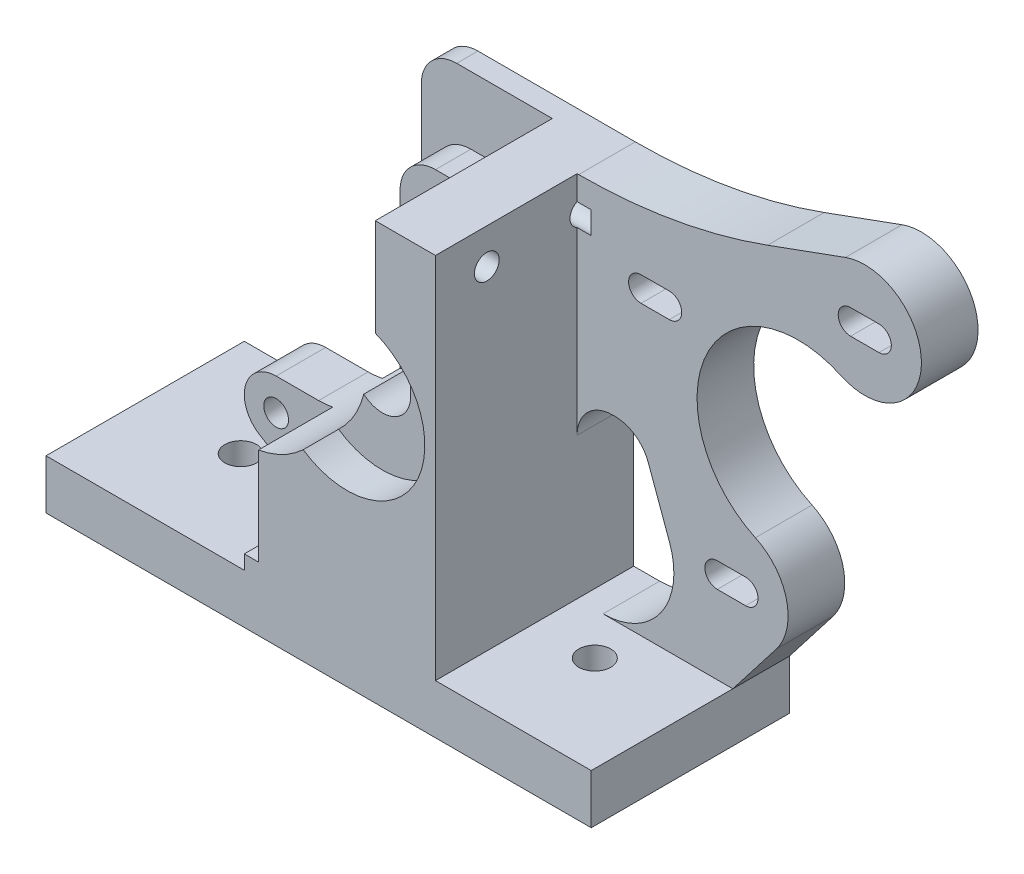
SolidWorks part; units mm, degrees
ref_plane "Front Plane" through (0, 0, 0) normal (0, 0, 1) x (1, 0, 0)
ref_plane "Top Plane" through (0, 0, 0) normal (0, 1, 0) x (1, 0, 0)
ref_plane "Right Plane" through (0, 0, 0) normal (1, 0, 0) x (0, 0, -1)
sketch "Sketch2" plane through (0, 0, 0) normal (0, 0, 1) x (1, 0, 0)
  line L0 (-39.5025, 0) -> (37.4975, 0) construction
  dimension "D1" = 77
sketch "Sketch4" plane through (0, 0, 0) normal (1, 0, 0) x (0, 0, -1)
  line L0 (0, 0) -> (0, 65) construction
  line L1 (0, 0) -> (-28, 0) construction
sketch "Sketch5" plane through (0, 0, 0) normal (0, 0, 1) x (1, 0, 0)
  line L0 (37.4975, 0) -> (-39.5025, 0)
  line L1 (-39.5025, 0) -> (-39.5025, 7)
  line L2 (-39.5025, 7) -> (-11.5, 7)
  line L3 (37.4975, 7) -> (37.4975, 0)
  line L4 (15.5, 7) -> (15.5, 32)
  line L5 (15.5, 32) -> (24.3525, 32)
  line L6 (24.3525, 32) -> (33.4518, 7)
  line L7 (56.1283, 60.187) -> (37.3016, 19.813) construction
  line L8 (-11.5, 7) -> (-11.5, 59)
  line L9 (-11.5, 59) -> (29.4767, 59)
  line L10 (29.4767, 59) -> (53.3922, 67.7045)
  line L11 (3, 0) -> (3, 59) construction
  line L12 (26.528, 49.4133) -> (37.3016, 19.813) construction
  line L13 (26.528, 49.4133) -> (56.1283, 60.187) construction
  line L14 (37.3016, 19.813) -> (66.902, 30.5867) construction
  line L15 (56.1283, 60.187) -> (66.902, 30.5867) construction
  line L16 (37.4975, 7) -> (43.6268, 14.9148)
  line L17 (15.5, 7) -> (33.4518, 7)
  circle A0 centre (3, 35) radius 11 construction
  circle A1 centre (3, 35) radius 4
  circle A2 centre (3, 35) radius 33 construction
  circle A3 centre (46.715, 40) radius 11 construction
  circle A4 centre (37.3016, 19.813) radius 1.75 construction
  circle A5 centre (26.528, 49.4133) radius 1.75 construction
  circle A6 centre (56.1283, 60.187) radius 1.75 construction
  circle A7 centre (66.902, 30.5867) radius 1.75 construction
  arc A8 (52.7474, 52.9365) -> (53.3922, 67.7045) centre (56.1283, 60.187) ccw
  arc A9 (45.3016, 19.813) -> (40.6826, 27.0635) centre (37.3016, 19.813) ccw
  arc A10 (45.3016, 19.813) -> (43.6268, 14.9148) centre (37.3016, 19.813) cw
  arc A11 (52.7474, 52.9365) -> (40.6826, 27.0635) centre (46.715, 40) ccw
  dimension "D1" = 22
  dimension "D7" = 8
  dimension "D10" = 22
  dimension "D11" = 66
  dimension "D14" = 3.5
  dimension "D15" = 8
  dimension "D5" = 33
  dimension "D2" = 7
  dimension "D3" = 27
  dimension "D4" = 25
  dimension "D6" = 31.5
  dimension "D8" = 52
  dimension "D9" = 14.5
  dimension "D12" = 28
  dimension "D13" = 70
  dimension "D16" = 3
extrude "Boss-Extrude1" add sketch "Sketch5" along normal blind 8 contours A11 A8 L10 L9 L8 L2 L1 L0 L3 L17 L4 L5 L6 A9 A1 region at (14.232, 31.6574, 0)
sketch "Sketch6" plane through (0, 0, 8) normal (0, 0, 1) x (1, 0, 0)
  line L0 (37.4975, 0) -> (-39.5025, 0) construction
  line L1 (-39.5025, 0) -> (-39.5025, 7) construction
  line L2 (-39.5025, 7) -> (-11.5, 7) construction
  line L3 (-11.5, 7) -> (-11.5, 59) construction
  line L4 (37.4975, 0) -> (-39.5025, 0)
  line L5 (-39.5025, 0) -> (-39.5025, 7)
  line L6 (-39.5025, 7) -> (-11.5, 7)
  line L7 (-11.5, 7) -> (-11.5, 59)
  line L8 (37.4975, 0) -> (37.4975, 7)
  line L9 (37.4975, 7) -> (15.5, 7)
  line L10 (15.5, 7) -> (15.5, 59)
  line L11 (-11.5, 59) -> (29.4767, 59) construction
  line L12 (15.5, 59) -> (-11.5, 59)
  line L13 (37.4975, 7) -> (37.4975, 0) construction
  circle A0 centre (3, 35) radius 4 construction
  circle A1 centre (3, 35) radius 4
extrude "Boss-Extrude2" add sketch "Sketch6" along normal blind 20
sketch "Sketch7" plane through (0, 0, 0) normal (0, -1, 0) x (1, 0, 0)
  line L0 (37.4975, 28) -> (-39.5025, 0) construction
  line L1 (-39.5025, 28) -> (37.4975, 0) construction
  circle A0 centre (-1.0025, 14) radius 7.875
  dimension "D1" = 15.75
extrude "Cut-Extrude1" cut sketch "Sketch7" against normal blind 4
ref_axis "Axis1" through (-1.0025, 4, 14) along (0, -1, 0)
sketch "Sketch8" plane through (0, 59, 0) normal (0, 1, 0) x (1, 0, 0)
  circle A0 centre (-1.0025, -14) radius 1.75
  dimension "D1" = 3.5
extrude "Cut-Extrude2" cut sketch "Sketch8" against normal blind 64
sketch "Sketch9" plane through (0, 0, 0) normal (0, -1, 0) x (1, 0, 0)
  line L0 (37.4975, 14) -> (-39.5025, 14) construction
  line L1 (37.4975, 28) -> (37.4975, 0) construction
  line L2 (-39.5025, 28) -> (-39.5025, 0) construction
  circle A0 centre (23.9975, 14) radius 2.25
  circle A1 centre (-26.0025, 14) radius 2.25
  dimension "D1" = 4.5
  dimension "D2" = 50
  dimension "D3" = 13.5
extrude "Cut-Extrude3" cut sketch "Sketch9" against normal blind 64
fillet "Fillet1" radius 10 1 edges
fillet "Fillet2" radius 78 1 edges at (29.4767, 59, 4)
fillet "Fillet3" radius 5 1 edges
sketch "Sketch10" plane through (0, 0, 0) normal (0, 0, -1) x (-1, 0, 0)
  circle A0 centre (-3, 35) radius 11
  dimension "D1" = 22
extrude "Cut-Extrude4" cut sketch "Sketch10" against normal blind 5
sketch "Sketch11" plane through (0, 0, 28) normal (0, 0, 1) x (1, 0, 0)
  circle A0 centre (3, 35) radius 11
  circle A1 centre (3, 35) radius 11 construction
extrude "Cut-Extrude5" cut sketch "Sketch11" against normal blind 5
sketch "Sketch13" plane through (-11.5, 0, 0) normal (-1, 0, 0) x (0, 0, 1)
  line L1 (14, 4) -> (14, 59) construction
  line L2 (28, 59) -> (0, 59) construction
  circle A0 centre (20.75, 54) radius 1.75
  circle A1 centre (7.25, 54) radius 1.75
  dimension "D1" = 3.5
  dimension "D3" = 6.75
  dimension "D2" = 6.75
  dimension "D4" = 5
extrude "Cut-Extrude7" cut sketch "Sketch13" against normal blind 29
fillet "Fillet4" radius 5 1 edges at (24.3525, 32, 4)
sketch "Sketch14" plane through (0, 0, 8) normal (0, 0, 1) x (1, 0, 0)
  line L0 (58.1283, 60.187) -> (54.1283, 60.187) construction
  line L1 (58.1283, 58.437) -> (54.1283, 58.437)
  line L2 (58.1283, 61.937) -> (54.1283, 61.937)
  line L3 (39.3016, 19.813) -> (35.3016, 19.813) construction
  line L4 (39.3016, 18.063) -> (35.3016, 18.063)
  line L5 (39.3016, 21.563) -> (35.3016, 21.563)
  line L6 (28.528, 49.4133) -> (24.528, 49.4133) construction
  line L7 (28.528, 47.6633) -> (24.528, 47.6633)
  line L8 (28.528, 51.1633) -> (24.528, 51.1633)
  circle A0 centre (56.1283, 60.187) radius 1.75 construction
  circle A1 centre (26.528, 49.4133) radius 1.75 construction
  circle A2 centre (37.3016, 19.813) radius 1.75 construction
  circle A3 centre (56.1283, 60.187) radius 1.75 construction
  circle A4 centre (26.528, 49.4133) radius 1.75 construction
  circle A5 centre (37.3016, 19.813) radius 1.75 construction
  arc A6 (58.1283, 58.437) -> (58.1283, 61.937) centre (58.1283, 60.187) ccw
  arc A7 (54.1283, 61.937) -> (54.1283, 58.437) centre (54.1283, 60.187) ccw
  arc A8 (39.3016, 18.063) -> (39.3016, 21.563) centre (39.3016, 19.813) ccw
  arc A9 (35.3016, 21.563) -> (35.3016, 18.063) centre (35.3016, 19.813) ccw
  arc A10 (28.528, 47.6633) -> (28.528, 51.1633) centre (28.528, 49.4133) ccw
  arc A11 (24.528, 51.1633) -> (24.528, 47.6633) centre (24.528, 49.4133) ccw
  point P11 (56.1283, 60.187)
  point P18 (37.3016, 19.813)
  point P23 (26.528, 49.4133)
  dimension "D1" = 1.75
  dimension "D2" = 4
extrude "Cut-Extrude8" cut sketch "Sketch14" against normal blind 29
sketch "Sketch15" plane through (0, 0, 0) normal (0, 0, -1) x (-1, 0, 0)
  line L4 (-39.3016, 16.063) -> (-35.3016, 16.063)
  line L5 (-35.3016, 23.563) -> (-39.3016, 23.563)
  line L6 (-39.3016, 16.063) -> (-35.3016, 16.063)
  line L7 (-35.3016, 23.563) -> (-39.3016, 23.563)
  line L10 (-24.528, 53.1633) -> (-28.528, 53.1633)
  line L11 (-28.528, 45.6633) -> (-24.528, 45.6633)
  line L12 (-24.528, 53.1633) -> (-28.528, 53.1633)
  line L13 (-28.528, 45.6633) -> (-24.528, 45.6633)
  line L16 (-54.1283, 63.937) -> (-58.1283, 63.937)
  line L17 (-58.1283, 56.437) -> (-54.1283, 56.437)
  line L18 (-54.1283, 63.937) -> (-58.1283, 63.937)
  line L19 (-58.1283, 56.437) -> (-54.1283, 56.437)
  arc A4 (-39.3016, 23.563) -> (-39.3016, 16.063) centre (-39.3016, 19.813) ccw
  arc A5 (-35.3016, 16.063) -> (-35.3016, 23.563) centre (-35.3016, 19.813) ccw
  arc A6 (-39.3016, 23.563) -> (-39.3016, 16.063) centre (-39.3016, 19.813) ccw
  arc A7 (-35.3016, 16.063) -> (-35.3016, 23.563) centre (-35.3016, 19.813) ccw
  arc A10 (-24.528, 45.6633) -> (-24.528, 53.1633) centre (-24.528, 49.4133) ccw
  arc A11 (-28.528, 53.1633) -> (-28.528, 45.6633) centre (-28.528, 49.4133) ccw
  arc A12 (-24.528, 45.6633) -> (-24.528, 53.1633) centre (-24.528, 49.4133) ccw
  arc A13 (-28.528, 53.1633) -> (-28.528, 45.6633) centre (-28.528, 49.4133) ccw
  arc A16 (-54.1283, 56.437) -> (-54.1283, 63.937) centre (-54.1283, 60.187) ccw
  arc A17 (-58.1283, 63.937) -> (-58.1283, 56.437) centre (-58.1283, 60.187) ccw
  arc A18 (-54.1283, 56.437) -> (-54.1283, 63.937) centre (-54.1283, 60.187) ccw
  arc A19 (-58.1283, 63.937) -> (-58.1283, 56.437) centre (-58.1283, 60.187) ccw
  dimension "D1" = 2
  dimension "D2" = 2
  dimension "D3" = 2
extrude "Cut-Extrude9" cut sketch "Sketch15" against normal blind 3
sketch "Sketch18" plane through (0, 0, 28) normal (0, 0, 1) x (1, 0, 0)
  line L0 (3, 35) -> (-11.7525, 35) construction
  line L8 (0.7475, 38.3055) -> (0.7475, 59) construction
  circle A0 centre (-11.7525, 35) radius 12.5
  dimension "D1" = 25
extrude "Cut-Extrude10" cut sketch "Sketch18" against normal up to surface (20 mm away) up to face at (26.528, 49.4133, 8)
ref_plane "Plane1" through (0, 0, 14) normal (0, 0, 1) x (1, 0, 0)
sketch "Sketch19" plane through (0, 0, 14) normal (0, 0, 1) x (1, 0, 0)
  line L0 (-19.8664, 14.1724) -> (-11.5, 9)
  line L1 (-11.5, 22.5025) -> (-11.5, 7) construction
  line L2 (-17.5019, 22.5) -> (-11.5, 22.5025)
  line L3 (-11.5, 22.5025) -> (-11.5, 9)
  line L4 (3, 35) -> (-20.2488, 35) construction
  circle A0 centre (-17.5, 18) radius 1.75
  arc A1 (-17.5019, 22.5) -> (-19.8664, 14.1724) centre (-17.5, 18) ccw
  dimension "D1" = 2
  dimension "D2" = 3.5
  dimension "D3" = 4.5
  dimension "D4" = 6
  dimension "D5" = 17
extrude "Boss-Extrude3" add sketch "Sketch19" along normal blind 3.5 and the other way blind 3.5
sketch "Sketch20" plane through (0, 0, 28) normal (0, 0, 1) x (1, 0, 0)
  line L1 (-11.5, 59) -> (7, 59)
  line L2 (-11.5, 59) -> (-11.5, 35)
  line L3 (-11.5, 35) -> (7, 35)
  line L4 (7, 59) -> (7, 35)
  arc A0 (0.3772, 31.9799) -> (0.3772, 38.0201) centre (3, 35) ccw construction
extrude "Cut-Extrude11" cut sketch "Sketch20" against normal up to surface (20 mm away) up to face at (-5.103, 35, 8)
sketch "Sketch21" plane through (0, 0, 8) normal (0, 0, 1) x (1, 0, 0)
  line L0 (7, 45.247) -> (7, 59) construction
  line L1 (-11.5, 59) -> (7, 59)
  line L2 (-11.5, 59) -> (-11.5, 49.5)
  line L3 (-11.5, 49.5) -> (7, 49.5)
  line L4 (7, 59) -> (7, 49.5)
  circle A1 centre (3, 35) radius 11 construction
  dimension "D1" = 3.5
extrude "Cut-Extrude12" cut sketch "Sketch21" against normal blind 5
ref_axis "Axis2" through (-17.5, 18, 10.5) along (0, 0, 1)
ref_plane "Plane2" through (0, 18, 0) normal (0, -1, 0) x (-1, 0, 0)
sketch "Sketch22" plane through (-11.5, 0, 0) normal (-1, 0, 0) x (0, 0, 1)
  line L0 (28, 24) -> (28, 45.247) construction
  line L1 (3, 49.5) -> (10.5, 49.5)
  line L2 (3, 49.5) -> (3, 9)
  line L3 (3, 9) -> (10.5, 9)
  line L4 (10.5, 49.5) -> (10.5, 9)
  line L5 (17.5, 9) -> (28, 9)
  line L6 (17.5, 9) -> (17.5, 39.3008)
  line L7 (17.5, 39.3008) -> (28, 39.3008)
  line L8 (28, 9) -> (28, 39.3008)
extrude "Cut-Extrude13" cut sketch "Sketch22" against normal blind 2
fillet "Fillet5" radius 5 2 edges at (-9.5, 49.5, 5.5) (-11.5, 59, 1.5)
sketch "Sketch23" plane through (0, 0, 8) normal (0, 0, 1) x (1, 0, 0)
  line L0 (-9.5, 35) -> (-8.5, 35) construction
  line L1 (-9.5, 44.5) -> (-9.5, 22.7046) construction
  line L2 (-9.5, 40) -> (-8.5, 40)
  line L3 (-9.5, 30) -> (-8.5, 30)
  arc A0 (-9.5, 40) -> (-9.5, 30) centre (-9.5, 35) ccw
  arc A1 (-8.5, 30) -> (-8.5, 40) centre (-8.5, 35) ccw
  arc A2 (7, 35) -> (0.3772, 31.9799) centre (3, 35) ccw construction
  arc A3 (7, 35) -> (0.3772, 31.9799) centre (3, 35) ccw construction
  point P4 (-9, 35)
  dimension "D1" = 5
  dimension "D2" = 1
extrude "Cut-Extrude14" cut sketch "Sketch23" against normal blind 2
equation "\"D3@Sketch9\"=(77-50)/2"
